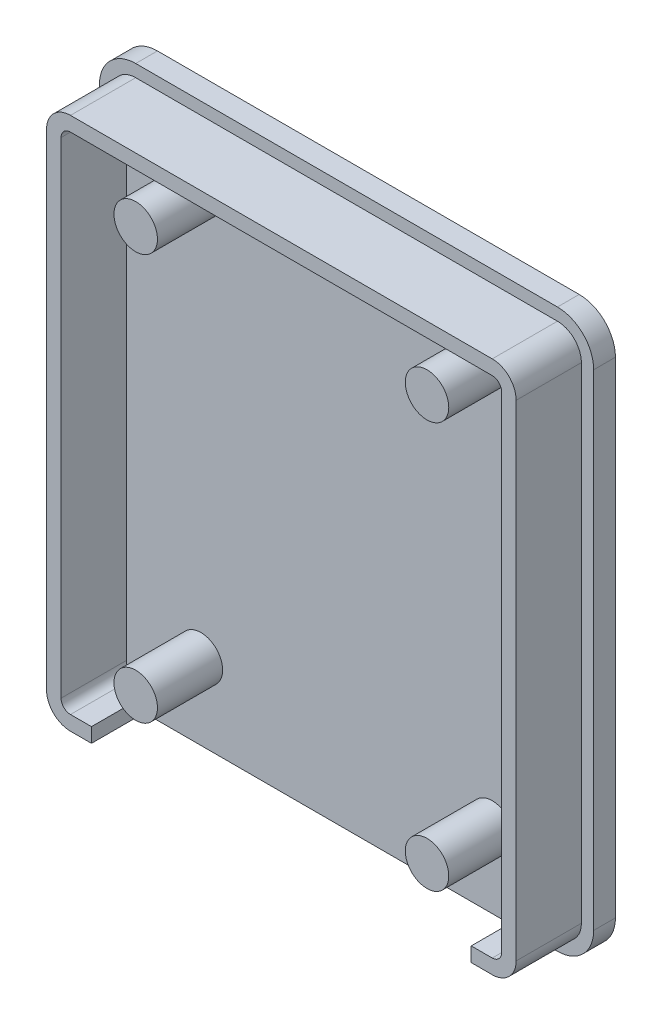
SolidWorks part; units mm, degrees
ref_plane "Front Plane" through (0, 0, 0) normal (0, 0, 1) x (1, 0, 0)
ref_plane "Top Plane" through (0, 0, 0) normal (0, 1, 0) x (1, 0, 0)
ref_plane "Right Plane" through (0, 0, 0) normal (1, 0, 0) x (0, 0, -1)
sketch "Sketch1" plane through (0, 0, 0) normal (0, 0, 1) x (1, 0, 0)
  line L0 (-16.2, -16.75) -> (-16.2, 16.75)
  line L1 (-14.55, -19.25) -> (14.55, -19.25)
  line L2 (-17.05, -16.75) -> (-17.05, 16.75)
  line L3 (-14.55, 19.25) -> (14.55, 19.25)
  line L4 (17.05, -16.75) -> (17.05, 16.75)
  line L5 (-17.05, -19.25) -> (17.05, 19.25) construction
  line L6 (-17.05, 19.25) -> (17.05, -19.25) construction
  line L7 (-14.55, 18.4) -> (14.55, 18.4)
  line L8 (16.2, -16.75) -> (16.2, 16.75)
  line L9 (-14.55, -18.4) -> (14.55, -18.4)
  line L10 (-15.2, -16.75) -> (-15.2, 16.75)
  line L11 (-14.55, 17.4) -> (14.55, 17.4)
  line L12 (15.2, -16.75) -> (15.2, 16.75)
  line L13 (-14.55, -17.4) -> (14.55, -17.4)
  line L14 (-13.1008, -17.4) -> (-13.1008, -18.4)
  line L15 (0, 0) -> (0, -19.25) construction
  line L16 (13.1008, -17.4) -> (13.1008, -18.4)
  line L17 (0, 0) -> (-17.05, 0) construction
  arc A0 (-14.55, -19.25) -> (-17.05, -16.75) centre (-14.55, -16.75) cw
  arc A1 (14.55, -19.25) -> (17.05, -16.75) centre (14.55, -16.75) ccw
  arc A2 (14.55, 19.25) -> (17.05, 16.75) centre (14.55, 16.75) cw
  arc A3 (-17.05, 16.75) -> (-14.55, 19.25) centre (-14.55, 16.75) cw
  arc A4 (-16.2, 16.75) -> (-14.55, 18.4) centre (-14.55, 16.75) cw
  arc A5 (14.55, 18.4) -> (16.2, 16.75) centre (14.55, 16.75) cw
  arc A6 (14.55, -18.4) -> (16.2, -16.75) centre (14.55, -16.75) ccw
  arc A7 (-14.55, -18.4) -> (-16.2, -16.75) centre (-14.55, -16.75) cw
  arc A8 (-15.2, 16.75) -> (-14.55, 17.4) centre (-14.55, 16.75) cw
  arc A9 (14.55, 17.4) -> (15.2, 16.75) centre (14.55, 16.75) cw
  arc A10 (14.55, -17.4) -> (15.2, -16.75) centre (14.55, -16.75) ccw
  arc A11 (-14.55, -17.4) -> (-15.2, -16.75) centre (-14.55, -16.75) cw
  circle A12 centre (-10.05, 14) radius 1.5
  circle A14 centre (10.05, 14) radius 1.5
  circle A15 centre (10.05, -14) radius 1.5
  circle A16 centre (-10.05, -14) radius 1.5
  point P0 (0, 0)
  dimension "D3" = 2.5
  dimension "D7" = 3
  dimension "D1" = 34.1
  dimension "D2" = 38.5
  dimension "D6" = 26.2015
  dimension "D8" = 28
  dimension "D9" = 20.1
  dimension "D4" = 0.85
  dimension "D5" = 1
extrude "Boss-Extrude1" add sketch "Sketch1" along normal blind 1.5 contours A12 | A16 | A14 | A15 | A11 L13 A10 L12 A9 L11 A8 L10 A14 A12 A15 A16 | L13 A11 L10 A8 L11 A9 L12 A10 L16 L9 A6 L8 A5 L7 A4 L0 A7 L14 | A3 L2 A0 L1 A1 L4 A2 L3 L9 A7 L0 A4 L7 A5 L8 A6 | L16 L13 L14 L9 region at (-15.7097, 0, 0) region at (0, -17.9, 0) region at (0, 0, 0) region at (-15.9541, -18.1541, 0) region at (-10.05, 14, 0) region at (10.05, 14, 0) region at (10.05, -14, 0) region at (-10.05, -14, 0)
extrude "Boss-Extrude2" add sketch "Sketch1<3>" along normal blind 6 contours L13 A11 L10 A8 L11 A9 L12 A10 L16 L9 A6 L8 A5 L7 A4 L0 A7 L14 | A12 | A16 | A15 | A14 region at (-15.7097, 0, 0) region at (-10.05, 14, 0) region at (10.05, 14, 0) region at (10.05, -14, 0) region at (-10.05, -14, 0)
sketch "Sketch1<3>" plane through (0, 0, 0) normal (0, 0, 1) x (1, 0, 0) same geometry as "Sketch1"
